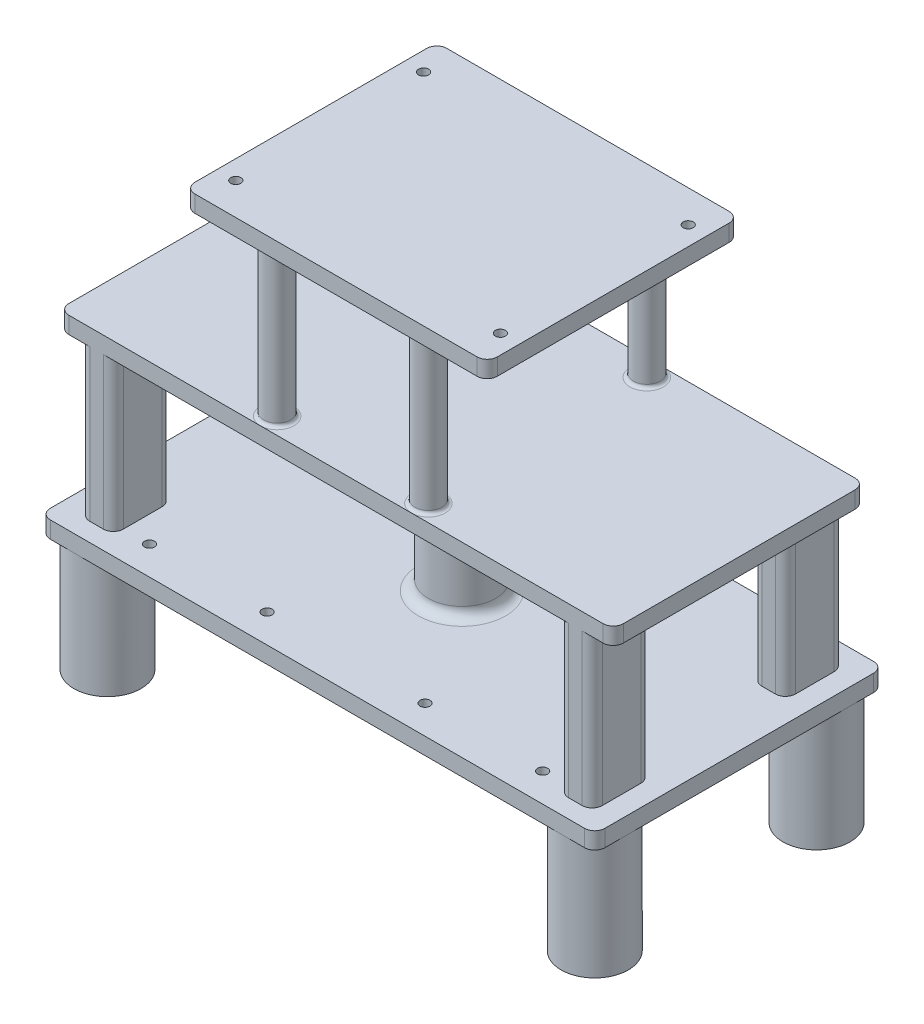
SolidWorks part; units mm, degrees
ref_plane "Front Plane" through (0, 0, 0) normal (0, 0, 1) x (1, 0, 0)
ref_plane "Top Plane" through (0, 0, 0) normal (0, 1, 0) x (1, 0, 0)
ref_plane "Right Plane" through (0, 0, 0) normal (1, 0, 0) x (0, 0, -1)
sketch "Sketch1" plane through (0, 0, 0) normal (0, 1, 0) x (1, 0, 0)
  line L1 (-82.5, 43) -> (82.5, 43)
  line L2 (-82.5, 43) -> (-82.5, -43)
  line L3 (-82.5, -43) -> (82.5, -43)
  line L4 (82.5, 43) -> (82.5, -43)
  line L5 (-82.5, 43) -> (82.5, -43) construction
  line L6 (-82.5, -43) -> (82.5, 43) construction
  circle A0 centre (-72.5, -33) radius 10
  circle A1 centre (-72.5, 33) radius 10
  circle A2 centre (72.5, 33) radius 10
  circle A3 centre (72.5, -33) radius 10
  circle A4 centre (-72.5, -33) radius 5
  circle A5 centre (-72.5, 33) radius 5
  circle A6 centre (72.5, 33) radius 5
  circle A7 centre (72.5, -33) radius 5
  point P0 (0, 0)
  dimension "D3" = 20
  dimension "D4" = 10
  dimension "D1" = 165
  dimension "D2" = 86
extrude "Boss-Extrude1" add sketch "Sketch1" along normal blind 35 contours A0 A4 | A1 A5 | A3 A7 | A2 A6 region at (-65.6289, 0, -39.8711) region at (79.3711, 0, -39.8711) region at (-72.5, 0, 23.2828) region at (79.3711, 0, 39.8711)
ref_plane "Plane1" through (0, 35, 0) normal (0, 1, 0) x (1, 0, 0)
sketch "Sketch2" plane through (0, 35, 0) normal (0, 1, 0) x (1, 0, 0)
  line L1 (-82.5, 43) -> (82.5, 43)
  line L2 (-82.5, 43) -> (-82.5, -43)
  line L3 (-82.5, -43) -> (82.5, -43)
  line L4 (82.5, 43) -> (82.5, -43)
  line L5 (-82.5, 43) -> (82.5, -43) construction
  line L6 (-82.5, -43) -> (82.5, 43) construction
  point P0 (0, 0)
  point P5 (0, 0)
  point P6 (0, 0)
extrude "Boss-Extrude2" add sketch "Sketch2" along normal blind 5
sketch "Sketch3" plane through (0, 40, 0) normal (0, 1, 0) x (1, 0, 0)
  line L0 (-82.5, 43) -> (-82.5, -43) construction
  line L1 (-62.5, 37.5) -> (-19.5, 37.5)
  line L2 (-62.5, 37.5) -> (-62.5, -37.5)
  line L3 (-62.5, -37.5) -> (-19.5, -37.5)
  line L4 (-19.5, 37.5) -> (-19.5, -37.5)
  line L5 (-62.5, 37.5) -> (-19.5, -37.5) construction
  line L6 (-62.5, -37.5) -> (-19.5, 37.5) construction
  line L11 (-58.5, -34.5) -> (-62.5, -34.5) construction
  line L12 (-58.5, -34.5) -> (-58.5, -37.5) construction
  line L13 (82.5, 43) -> (-82.5, 43) construction
  circle A0 centre (-58.5, 34.5) radius 1.5
  circle A1 centre (-23.5, 34.5) radius 1.5
  circle A2 centre (-58.5, -34.5) radius 1.5
  circle A3 centre (-23.5, -34.5) radius 1.5
  point P0 (-41, 0)
  point P9 (0, 0)
  dimension "D5" = 3
  dimension "D1" = 43
  dimension "D2" = 75
  dimension "D3" = 20
  dimension "D4" = 5.5
  dimension "D6" = 69
  dimension "D7" = 35
  dimension "D8" = 3
  dimension "D9" = 4
extrude "Cut-Extrude1" cut sketch "Sketch3" against normal up to surface (5 mm away) contours A0 | A1 | A2 | A3 up to face at (0, 35, 0)
mirror "Mirror1" about plane through (0, 0, 0) normal (1, 0, 0) of "Cut-Extrude1"
ref_plane "Plane2" through (0, 40, 0) normal (0, 1, 0) x (1, 0, 0)
sketch "Sketch4" plane through (0, 40, 0) normal (0, 1, 0) x (1, 0, 0)
  line L0 (-76.25, 43) -> (-76.25, -43) construction
  line L1 (-76.25, 37.5) -> (-66.25, 37.5)
  line L2 (-76.25, 37.5) -> (-76.25, -37.5)
  line L3 (-76.25, -37.5) -> (-66.25, -37.5)
  line L4 (-66.25, 37.5) -> (-66.25, -37.5)
  line L5 (-76.25, 37.5) -> (-66.25, -37.5) construction
  line L6 (-76.25, -37.5) -> (-66.25, 37.5) construction
  line L7 (66.25, 37.5) -> (76.25, 37.5)
  line L8 (66.25, 37.5) -> (66.25, -37.5)
  line L9 (66.25, -37.5) -> (76.25, -37.5)
  line L10 (76.25, 37.5) -> (76.25, -37.5)
  line L11 (66.25, 37.5) -> (76.25, -37.5) construction
  line L12 (66.25, -37.5) -> (76.25, 37.5) construction
  line L13 (82.5, 43) -> (-82.5, 43) construction
  line L14 (-82.5, -43) -> (82.5, -43) construction
  line L15 (-82.5, -34.5) -> (-60, -34.5) construction
  line L16 (-82.5, 43) -> (-82.5, -43) construction
  line L17 (-58.5142, -33.0001) -> (-58.5142, -35.9999) construction
  line L18 (82.5, -43) -> (82.5, 43) construction
  line L20 (-76.25, 20) -> (-66.25, 20)
  line L21 (-76.25, 20) -> (-76.25, -20)
  line L22 (-76.25, -20) -> (-66.25, -20)
  line L23 (-66.25, 20) -> (-66.25, -20)
  line L24 (-76.25, 20) -> (-66.25, -20) construction
  line L25 (-76.25, -20) -> (-66.25, 20) construction
  line L26 (66.25, 20) -> (76.25, 20)
  line L27 (66.25, 20) -> (66.25, -20)
  line L28 (66.25, -20) -> (76.25, -20)
  line L29 (76.25, 20) -> (76.25, -20)
  line L30 (66.25, 20) -> (76.25, -20) construction
  line L31 (66.25, -20) -> (76.25, 20) construction
  circle A0 centre (0, 0) radius 10
  circle A2 centre (-58.5, -34.5) radius 1.5 construction
  circle A3 centre (0, 0) radius 5
  point P2 (71.25, 0)
  point P4 (-71.25, 0)
  point P17 (-71.25, 0)
  point P20 (-76.25, 0)
  point P21 (-76.25, 0)
  point P31 (-58.5142, -34.5)
  point P32 (-71.25, -34.5)
  point P33 (-71.25, -37.5)
  point P41 (0, 0)
  point P43 (71.25, 0)
  dimension "D4" = 20
  dimension "D5" = 10
  dimension "D1" = 75
  dimension "D2" = 10
  dimension "D3" = 6.25
  dimension "D6" = 40
  dimension "D7" = 40
extrude "Boss-Extrude3" add sketch "Sketch4" along normal blind 45 contours L2 L20 L4 L1 | L22 L2 L3 L4 | A0 A3 | L8 L26 L10 L7 | L28 L8 L9 L10 region at (-71.25, 40, -28.75) region at (-71.25, 40, 28.75) region at (71.25, 40, -28.75) region at (71.25, 40, 28.75) region at (-9.7172, 40, 0)
ref_plane "Plane3" through (0, 85, 0) normal (0, 1, 0) x (1, 0, 0)
sketch "Sketch5" plane through (0, 85, 0) normal (0, 1, 0) x (1, 0, 0)
  line L1 (-82.5, 37.5) -> (82.5, 37.5)
  line L2 (-82.5, 37.5) -> (-82.5, -37.5)
  line L3 (-82.5, -37.5) -> (82.5, -37.5)
  line L4 (82.5, 37.5) -> (82.5, -37.5)
  line L5 (-82.5, 37.5) -> (82.5, -37.5) construction
  line L6 (-82.5, -37.5) -> (82.5, 37.5) construction
  point P0 (0, 0)
  point P5 (0, 0)
  dimension "D1" = 165
  dimension "D2" = 75
extrude "Boss-Extrude4" add sketch "Sketch5" along normal blind 5
sketch "Sketch6" plane through (0, 90, 0) normal (0, 1, 0) x (1, 0, 0)
  line L0 (-22.5, 37.5) -> (-22.5, 32.5) construction
  line L1 (82.5, 37.5) -> (-82.5, 37.5) construction
  line L2 (-82.5, -37.5) -> (82.5, -37.5) construction
  line L3 (-82.5, 37.5) -> (-82.5, -37.5) construction
  circle A0 centre (-22.5, 32.5) radius 4
  circle A2 centre (-22.5, -32.5) radius 4
  point P0 (0, 0)
  point P2 (0, 0)
  point P3 (0, 0)
  point P10 (0, 0)
  dimension "D1" = 8
  dimension "D2" = 5
  dimension "D3" = 5
  dimension "D4" = 60
extrude "Boss-Extrude5" add sketch "Sketch6" along normal blind 45
mirror "Mirror2" about plane through (0, 0, 0) normal (1, 0, 0) of "Boss-Extrude5"
ref_plane "Plane4" through (0, 135, 0) normal (0, 1, 0) x (1, 0, 0)
sketch "Sketch7" plane through (0, 135, 0) normal (0, 1, 0) x (1, 0, 0)
  line L1 (-45, 37.5) -> (45, 37.5)
  line L2 (-45, 37.5) -> (-45, -37.5)
  line L3 (-45, -37.5) -> (45, -37.5)
  line L4 (45, 37.5) -> (45, -37.5)
  line L5 (-45, 37.5) -> (45, -37.5) construction
  line L6 (-45, -37.5) -> (45, 37.5) construction
  point P0 (0, 0)
  point P5 (0, 0)
  point P6 (0, 0)
  dimension "D1" = 90
  dimension "D2" = 75
extrude "Boss-Extrude6" add sketch "Sketch7" along normal blind 5
sketch "Sketch8" plane through (0, 140, 0) normal (0, 1, 0) x (1, 0, 0)
  line L1 (-42.25, 31) -> (42.25, 31)
  line L2 (-42.25, 31) -> (-42.25, -31)
  line L3 (-42.25, -31) -> (42.25, -31)
  line L4 (42.25, 31) -> (42.25, -31)
  line L5 (-42.25, 31) -> (42.25, -31) construction
  line L6 (-42.25, -31) -> (42.25, 31) construction
  circle A0 centre (-39.37, 27.94) radius 1.5
  circle A1 centre (-39.37, -27.94) radius 1.5
  circle A2 centre (39.37, 27.94) radius 1.5
  circle A3 centre (39.37, -27.94) radius 1.5
  point P0 (0, 0)
  point P14 (0, 0)
  point P15 (0, 0)
  point P16 (-39.121, 25.7282)
  point P17 (0, 0)
  point P18 (0, 0)
  point P19 (0, 0)
  dimension "D3" = 3
  dimension "D1" = 84.5
  dimension "D2" = 62
  dimension "D4" = 55.88
  dimension "D5" = 78.74
  dimension "D6" = 3.06
  dimension "D7" = 2.88
extrude "Cut-Extrude3" cut sketch "Sketch8" against normal up to surface (5 mm away) contours A3 | A1 | A2 | A0 region at (39.37, 140, 27.94) up to face at (-22.5, 135, 36.5)
fillet "Fillet2" radius 3 28 edges at (-76.25, 62.5, -20) (-76.25, 62.5, 37.5) (-76.25, 62.5, -37.5) (-66.25, 62.5, -37.5) (-66.25, 62.5, -20) (-66.25, 62.5, 37.5) (-76.25, 62.5, 20) (-66.25, 62.5, 20) (66.25, 62.5, 20) (66.25, 62.5, 37.5) (76.25, 62.5, 20) (76.25, 62.5, 37.5) (66.25, 62.5, -20) (76.25, 62.5, -20) (66.25, 62.5, -37.5) (76.25, 62.5, -37.5) (45, 137.5, -37.5) (82.5, 87.5, -37.5) (82.5, 87.5, 37.5) (45, 137.5, 37.5) (-45, 137.5, -37.5) (-45, 137.5, 37.5) (-82.5, 87.5, 37.5) (-82.5, 87.5, -37.5) (-82.5, 37.5, -43) (82.5, 37.5, -43) (82.5, 37.5, 43) (-82.5, 37.5, 43)
fillet "Fillet3" radius 3 2 edges at (0, 85, 10) (0, 40, 10)
fillet "Fillet4" radius 1 8 edges at (22.5, 135, 36.5) (22.5, 90, -28.5) (-22.5, 90, -28.5) (-22.5, 90, 36.5) (-22.5, 135, -28.5) (-22.5, 135, 36.5) (22.5, 135, -28.5) (22.5, 90, 36.5)
